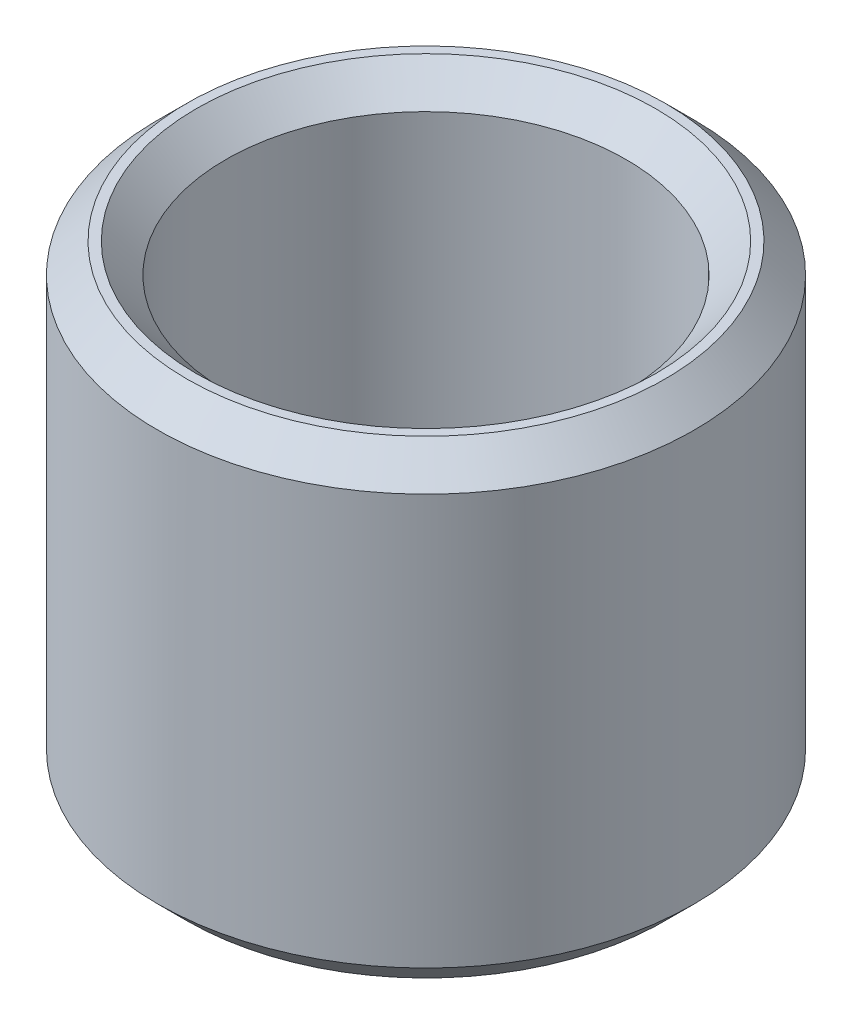
SolidWorks part; units mm, degrees
ref_plane "Front Plane" through (0, 0, 0) normal (0, 0, 1) x (1, 0, 0)
ref_plane "Top Plane" through (0, 0, 0) normal (0, 1, 0) x (1, 0, 0)
ref_plane "Right Plane" through (0, 0, 0) normal (1, 0, 0) x (0, 0, -1)
sketch "Sketch1" plane through (0, 0, 0) normal (0, 1, 0) x (1, 0, 0)
  circle A0 centre (0, 0) radius 25
  dimension "SLEEVE_OD" = 50
extrude "Boss-Extrude1" add sketch "Sketch1" along normal blind 43.6998
sketch "Sketch2" plane through (0, 0, 0) normal (0, 1, 0) x (1, 0, 0)
  circle A0 centre (0, 0) radius 18.6459
  dimension "BORE_D" = 37.2917
extrude "Cut-Extrude1" cut sketch "Sketch2" along normal through all
chamfer "Chamfer1" distance 2.7383 angle 45 4 edges at (0, 43.6998, 18.6459) (0, 0, 18.6459) (0, 0, 25) (0, 43.6998, 25)
